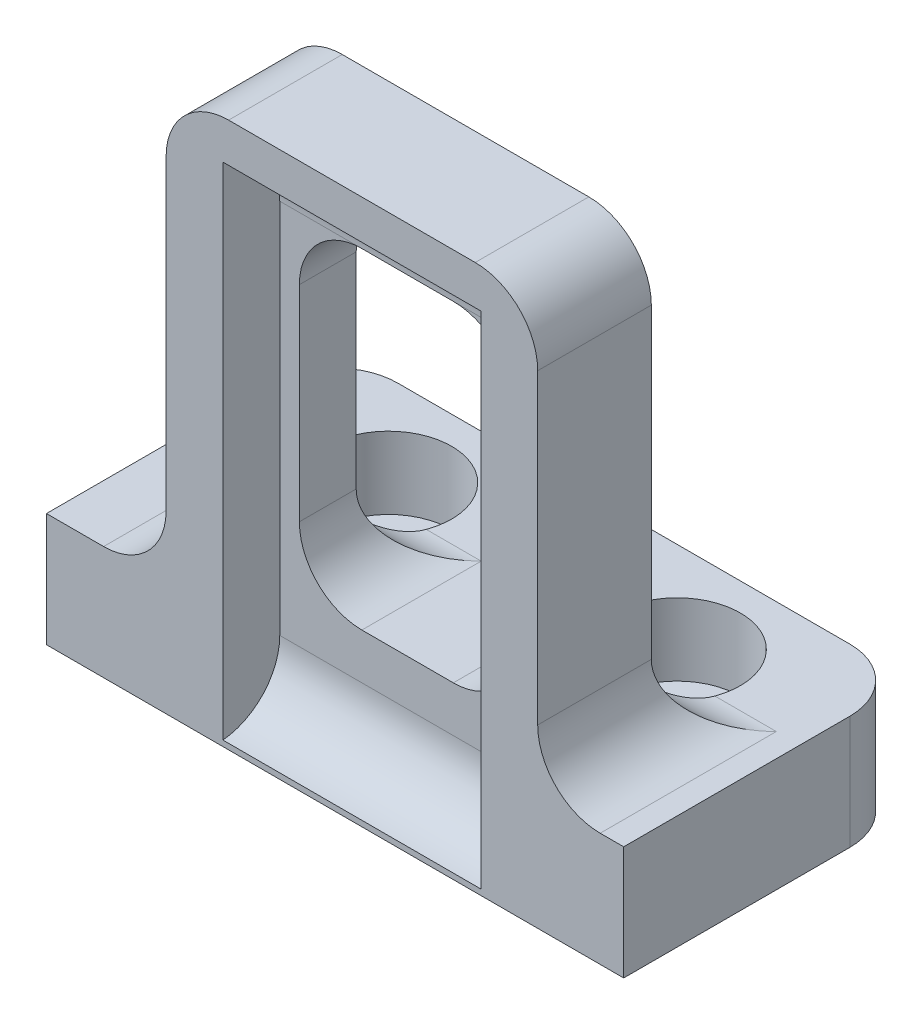
SolidWorks part; units mm, degrees
ref_plane "Front Plane" through (0, 0, 0) normal (0, 0, 1) x (1, 0, 0)
ref_plane "Top Plane" through (0, 0, 0) normal (0, 1, 0) x (1, 0, 0)
ref_plane "Right Plane" through (0, 0, 0) normal (1, 0, 0) x (0, 0, -1)
sketch "Sketch1" plane through (0, 0, 0) normal (0, 1, 0) x (1, 0, 0)
  line L1 (0, 0) -> (50.8, 0)
  line L2 (0, 0) -> (0, 25.4)
  line L3 (0, 25.4) -> (50.8, 25.4)
  line L4 (50.8, 0) -> (50.8, 25.4)
  dimension "D1" = 50.8
  dimension "D2" = 25.4
extrude "Boss-Extrude1" add sketch "Sketch1" along normal blind 10
sketch "Sketch2" plane through (0, 10, 0) normal (0, 1, 0) x (1, 0, 0)
  line L5 (0, 0) -> (50.8, 0) construction
  line L6 (43.2315, 10) -> (10.5315, 10)
  line L7 (43.2315, 10) -> (43.2315, 0)
  line L8 (43.2315, 0) -> (10.5315, 0)
  line L9 (10.5315, 10) -> (10.5315, 0)
  line L10 (43.2315, 10) -> (10.5315, 0) construction
  line L11 (43.2315, 0) -> (10.5315, 10) construction
  point P0 (26.8815, 5)
  dimension "D1" = 32.7
  dimension "D2" = 10
extrude "Boss-Extrude3" add sketch "Sketch2" along normal blind 38
sketch "Sketch3" plane through (0, 0, 0) normal (0, 0, 1) x (1, 0, 0)
  line L1 (15.5315, 0.5) -> (38.2315, 0.5)
  line L2 (15.5315, 0.5) -> (15.5315, 44.55)
  line L3 (15.5315, 44.55) -> (38.2315, 44.55)
  line L4 (38.2315, 0.5) -> (38.2315, 44.55)
  line L5 (15.5315, 0.5) -> (38.2315, 44.55) construction
  line L6 (15.5315, 44.55) -> (38.2315, 0.5) construction
  line L7 (0, 0) -> (50.8, 0) construction
  point P0 (26.8815, 22.525)
  dimension "D1" = 0.5
  dimension "D2" = 22.7
  dimension "D3" = 44.05
extrude "Cut-Extrude1" cut sketch "Sketch3" against normal blind 5
fillet "Fillet1" radius 5.5 2 edges at (26.8815, 0.5, -5) (26.8815, 44.55, -5)
sketch "Sketch4" plane through (0, 0, -5) normal (0, 0, 1) x (1, 0, 0)
  line L0 (38.2315, 39.0728) -> (15.5315, 39.0728) construction
  line L1 (17.2579, 10) -> (36.3079, 10)
  line L2 (17.2579, 10) -> (17.2579, 39.0728)
  line L3 (17.2579, 39.0728) -> (36.3079, 39.0728)
  line L4 (36.3079, 10) -> (36.3079, 39.0728)
  line L5 (17.2579, 10) -> (36.3079, 39.0728) construction
  line L6 (17.2579, 39.0728) -> (36.3079, 10) construction
  line L8 (43.2315, 10) -> (50.8, 10) construction
  point P0 (26.7829, 24.5364)
  dimension "D1" = 0
  dimension "D2" = 0
  dimension "D3" = 19.05
extrude "Cut-Extrude2" cut sketch "Sketch4" against normal through all
sketch "Sketch5" plane through (0, 10, 0) normal (0, 1, 0) x (1, 0, 0)
  line L0 (0, 25.4) -> (0, 0) construction
  line L1 (50.8, 0) -> (50.8, 25.4) construction
  line L2 (50.8, 25.4) -> (0, 25.4) construction
  point P0 (38.1, 17.4)
  point P1 (12.7, 17.4)
  dimension "D1" = 12.7
  dimension "D2" = 12.7
  dimension "D3" = 8
  dimension "D4" = 8
hole_wizard "CBORE for 1/4 Socket Head Cap Screw1" positions "Sketch6" profile "Sketch7" counterbore size "1/4" standard "ANSI Inch" end condition through all
sketch "Sketch6" plane through (0, 10, 0) normal (0, 1, 0) x (1, 0, 0)
  point P0 (38.1, 17.4)
  point P3 (12.7, 17.4)
sketch "Sketch7" plane through (38.1, 10, -17.4) normal (1, 0, 0) x (0, 0, 1)
  line L0 (0, 0) -> (0, 10)
  line L1 (0, 10) -> (3.3782, 10)
  line L3 (3.3782, 10) -> (3.3782, 6.35)
  line L4 (3.3782, 6.35) -> (5.5562, 6.35)
  line L5 (5.5562, 6.35) -> (5.5562, 0)
  line L7 (5.5562, 0) -> (0, 0)
  line L11 (0, -6.35) -> (0, 107.95) construction
  dimension "Thru Hole Dia." = 6.7564
  dimension "Thru Hole Depth" = 10
  dimension "C'Bore Dia." = 11.1125
  dimension "C'Bore Depth" = 6.35
fillet "Fillet2" radius 5.5 10 edges at (0, 5, -25.4) (50.8, 5, -25.4) (43.2315, 48, -5) (10.5315, 48, -5) (17.2579, 39.0728, -7.5) (36.3079, 39.0728, -7.5) (17.2579, 10, -7.5) (36.3079, 10, -7.5) (10.5315, 10, -5) (43.2315, 10, -5)
fillet "Fillet3" radius 5.5 2 edges at (13.8947, 10, -10) (39.7697, 10, -10)
